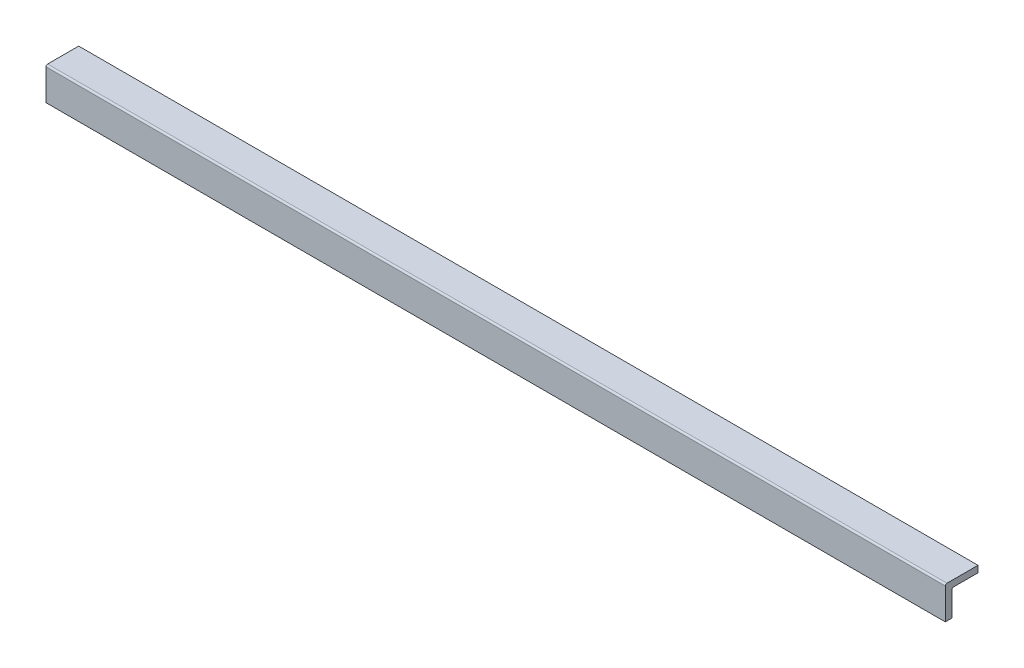
SolidWorks part; units mm, degrees
material "1060 Alloy"
ref_plane "Front Plane" through (0, 0, 0) normal (0, 0, 1) x (1, 0, 0)
ref_plane "Top Plane" through (0, 0, 0) normal (0, 1, 0) x (1, 0, 0)
ref_plane "Right Plane" through (0, 0, 0) normal (1, 0, 0) x (0, 0, -1)
sketch "Sketch1" plane through (0, 0, 0) normal (1, 0, 0) x (0, 0, -1)
  line L0 (0, -10) -> (0, -0.5)
  line L1 (0.5, 0) -> (10, 0)
  line L2 (10, 0) -> (10, -2)
  line L3 (10, -2) -> (2.5, -2)
  line L4 (0, -10) -> (2, -10)
  line L5 (2, -10) -> (2, -2.5)
  arc A0 (0, -0.5) -> (0.5, 0) centre (0.5, -0.5) cw
  arc A1 (2.5, -2) -> (2, -2.5) centre (2.5, -2.5) ccw
  point P10 (0, 0)
  dimension "D3" = 0.5
  dimension "D1" = 10
  dimension "D2" = 2
extrude "Boss-Extrude1" add sketch "Sketch1" along normal blind 137.5 and the other way blind 137.5
